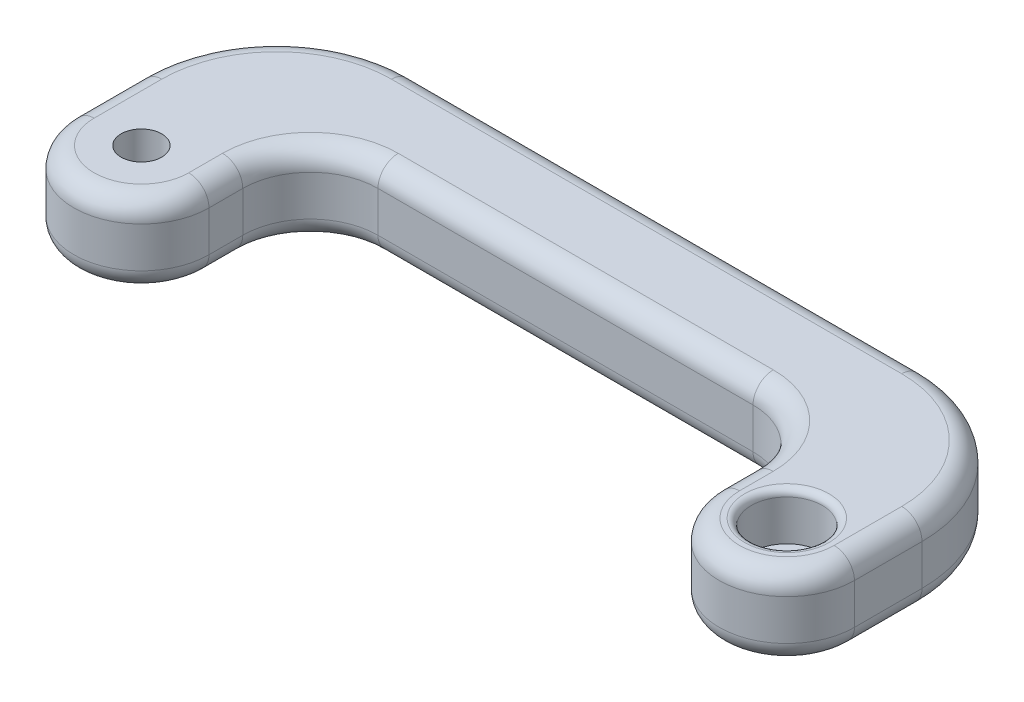
SolidWorks part; units mm, degrees
ref_plane "Front Plane" through (0, 0, 0) normal (0, 0, 1) x (1, 0, 0)
ref_plane "Top Plane" through (0, 0, 0) normal (0, 1, 0) x (1, 0, 0)
ref_plane "Right Plane" through (0, 0, 0) normal (1, 0, 0) x (0, 0, -1)
sketch "Sketch7" plane through (0, 0, 0) normal (0, 1, 0) x (1, 0, 0)
  line L2 (-105.5, 0) -> (-105.5, 30)
  line L3 (-85.5, 0) -> (-85.5, 15)
  line L4 (-105.5, 30) -> (-85.5, 30)
  line L6 (-85.5, 30) -> (10, 30)
  line L7 (-85.5, 15) -> (-10, 15)
  line L10 (10, 0) -> (10, 30.0013)
  line L11 (-10, 0) -> (-10, 15)
  line L12 (10, 30.0013) -> (-10, 30.0013)
  line L13 (-10, 30) -> (-10, 30.0013)
  arc A0 (-10, 0) -> (10, 0) centre (0, 0) ccw
  arc A1 (-105.5, 0) -> (-85.5, 0) centre (-95.5, 0) ccw
  circle A2 centre (-95.5, 0) radius 5
extrude "Boss-Extrude5" add sketch "Sketch7" along normal blind 12 contours L2 A1 L3 L7 L11 A0 L10 L6 L4 A2 region at (-46.2897, 0, -16.412)
sketch "Sketch8" plane through (0, 12, 0) normal (0, 1, 0) x (1, 0, 0)
  circle A0 centre (0, 0) radius 6
fillet "Fillet2" radius 20 2 edges at (10, 6, -30) (-105.5, 6, -30)
fillet "Fillet3" radius 10 2 edges at (-10, 6, -15) (-85.5, 6, -15)
fillet "Fillet5" radius 3 24 edges at (-47.75, 12, -30) (4.1421, 12, -24.1421) (10, 12, -5) (0, 12, 10) (-10, 12, -2.5) (-12.9289, 12, -12.0711) (-47.75, 12, -15) (-82.5711, 12, -12.0711) (-85.5, 12, -2.5) (-95.5, 12, 10) (-105.5, 12, -5) (-105.5, 0, -5) (-95.5, 0, 10) (-85.5, 0, -2.5) (-82.5711, 0, -12.0711) (-47.75, 0, -15) (-12.9289, 0, -12.0711) (-10, 0, -2.5) (0, 0, 10) (10, 0, -5) (4.1421, 0, -24.1421) (-47.75, 0, -30) (-99.6421, 12, -24.1421) (-99.6421, 0, -24.1421)
sketch "Sketch10" plane through (0, 12, 0) normal (0, 1, 0) x (1, 0, 0)
  circle A0 centre (-95.5, 0) radius 5.1
sketch "Sketch11" plane through (0, 0, 0) normal (0, -1, 0) x (1, 0, 0)
  circle A0 centre (-95.5, 0) radius 5.25
  circle A1 centre (0, 0) radius 5.25
extrude "Cut-Extrude1" cut sketch "Sketch11" against normal blind 36
fillet "Fillet6" radius 1 4 edges at (-95.5, 12, 5.25) (0, 12, 5.25) (0, 0, -5.25) (-95.5, 0, -5.25)
sketch "Sketch12" plane through (0, 12, 0) normal (0, 1, 0) x (1, 0, 0)
  circle A0 centre (-95.5, 0) radius 6.25
  circle A1 centre (-95.5, 0) radius 3
extrude "Boss-Extrude6" add sketch "Sketch12" against normal blind 5
sketch "Sketch13" plane through (0, 0, 0) normal (0, -1, 0) x (1, 0, 0)
  circle A0 centre (0, 0) radius 6.25
  circle A1 centre (0, 0) radius 3
extrude "Boss-Extrude7" add sketch "Sketch13" against normal blind 5
